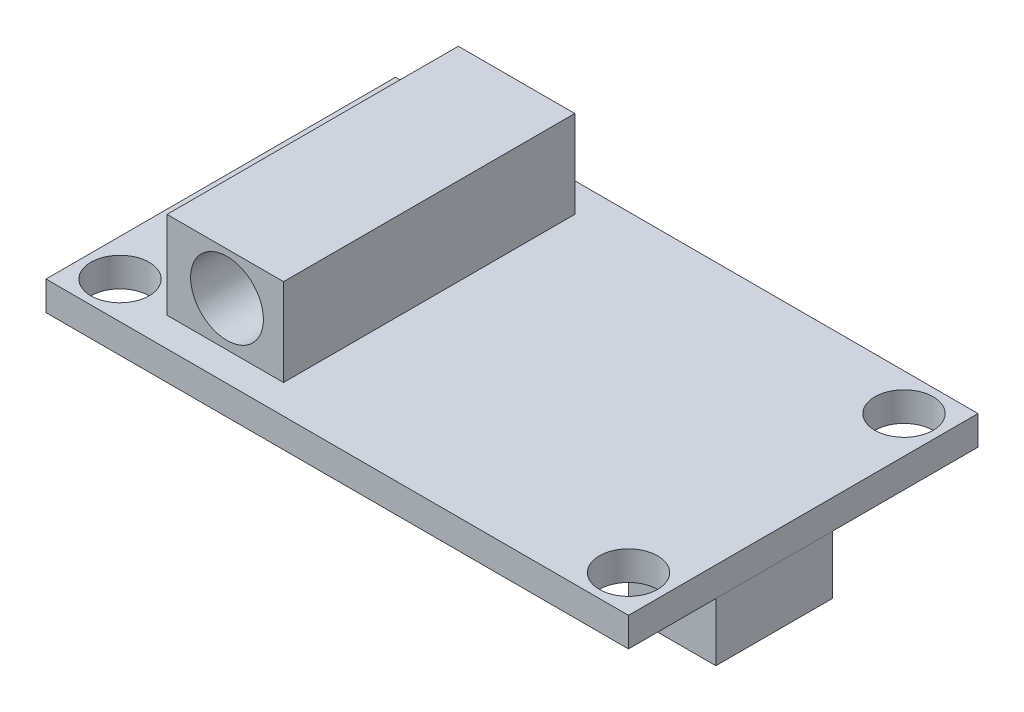
SolidWorks part; units mm, degrees
ref_plane "Front Plane" through (0, 0, 0) normal (0, 0, 1) x (1, 0, 0)
ref_plane "Top Plane" through (0, 0, 0) normal (0, 1, 0) x (1, 0, 0)
ref_plane "Right Plane" through (0, 0, 0) normal (1, 0, 0) x (0, 0, -1)
sketch "Sketch2" plane through (0, 0, 0) normal (0, 1, 0) x (1, 0, 0)
  line L0 (0, 0) -> (-15.875, 0) construction
  line L1 (-15.875, 9.525) -> (15.875, 9.525)
  line L2 (-15.875, 9.525) -> (-15.875, -9.525)
  line L3 (-15.875, -9.525) -> (15.875, -9.525)
  line L4 (15.875, 9.525) -> (15.875, -9.525)
  line L5 (-15.875, 9.525) -> (15.875, -9.525) construction
  line L6 (-15.875, -9.525) -> (15.875, 9.525) construction
  line L7 (-10.8653, 7.9375) -> (-4.5153, 7.9375)
  line L8 (-10.8653, 7.9375) -> (-10.8653, -7.9375)
  line L9 (-10.8653, -7.9375) -> (-4.5153, -7.9375)
  line L10 (-4.5153, 7.9375) -> (-4.5153, -7.9375)
  line L11 (-15.875, 5.5563) -> (-11.1125, 5.5563)
  line L12 (-15.875, 5.5563) -> (-15.875, -0.7937)
  line L13 (-15.875, -0.7937) -> (-11.1125, -0.7937)
  line L14 (-11.1125, 5.5563) -> (-11.1125, -0.7937)
  line L15 (0, 0) -> (0, 9.525) construction
  line L17 (11.1125, 1.5875) -> (15.875, 1.5875)
  line L18 (11.1125, 1.5875) -> (11.1125, -4.7625)
  line L19 (11.1125, -4.7625) -> (15.875, -4.7625)
  line L20 (15.875, 1.5875) -> (15.875, -4.7625)
  circle A0 centre (-13.8581, 7.5081) radius 1.5875
  circle A1 centre (-13.8581, -7.5081) radius 1.5875
  circle A2 centre (13.8581, -7.5081) radius 1.5875
  circle A3 centre (13.8581, 7.5081) radius 1.5875
  point P0 (0, 0)
  point P14 (-13.4938, 5.5563)
  dimension "D11" = 3.175
  dimension "D1" = 31.75
  dimension "D2" = 19.05
  dimension "D3" = 6.35
  dimension "D4" = 15.875
  dimension "D5" = 1.5875
  dimension "D6" = 3.9688
  dimension "D7" = 4.7625
  dimension "D8" = 6.35
  dimension "D9" = 2.0169
  dimension "D10" = 2.0169
  dimension "D12" = 4.7625
  dimension "D13" = 4.7625
  dimension "D14" = 6.35
extrude "Boss-Extrude1" add sketch "Sketch2" along normal blind 1.5875 contours L19 L18 L17 L4 L1 L2 L11 L14 L13 L3 A1 A0 L7 L10 L9 L8 A2 A3 | L12 L11 L14 L13 | L18 L17 L20 L19 | L8 L7 L10 L9 region at (1.8822, 0, 0.0583)
extrude "Boss-Extrude2" add sketch "Sketch2<5>" against normal blind 3.175 separate body contours L14 L11 L2 L13 | L18 L19 L4 L17 region at (-13.4938, 0, -2.3813) region at (13.4937, 0, 1.5875)
sketch "Sketch2<5>" plane through (0, 0, 0) normal (0, 1, 0) x (1, 0, 0) same geometry as "Sketch2"
extrude "Boss-Extrude3" add sketch "Sketch2<6>" along normal blind 4.7625 from surface contours L10 L7 L8 L9 region at (-7.6903, 0, 0) starting at face at (0, 1.5875, 0)
sketch "Sketch2<6>" plane through (0, 0, 0) normal (0, 1, 0) x (1, 0, 0) same geometry as "Sketch2"
sketch "Sketch3" plane through (0, 0, 7.9375) normal (0, 0, 1) x (1, 0, 0)
  circle A0 centre (-7.5966, 4.0184) radius 1.9844
  dimension "D1" = 3.9688
extrude "Cut-Extrude1" cut sketch "Sketch3" against normal blind 12.7625
